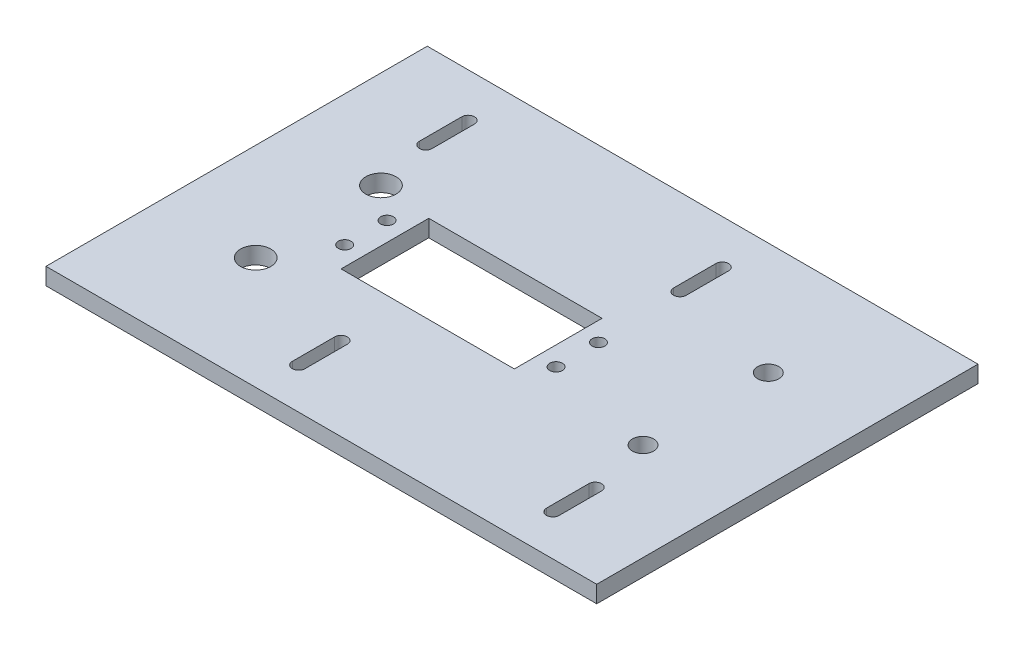
SolidWorks part; units mm, degrees
ref_plane "Front" through (0, 0, 0) normal (0, 0, 1) x (1, 0, 0)
ref_plane "Top" through (0, 0, 0) normal (0, 1, 0) x (1, 0, 0)
ref_plane "Right" through (0, 0, 0) normal (1, 0, 0) x (0, 0, -1)
sketch "Sketch1" plane through (0, 0, 0) normal (0, 1, 0) x (1, 0, 0)
  line L1 (-105, -51.6724) -> (25, -51.6724)
  line L2 (-105, -51.6724) -> (-105, 38.3276)
  line L3 (-105, 38.3276) -> (25, 38.3276)
  line L4 (25, -51.6724) -> (25, 38.3276)
  dimension "D2" = 90
  dimension "D1" = 130
extrude "Boss-Extrude1" add sketch "Sketch1" along normal blind 4
sketch "Sketch2" plane through (0, 4, 0) normal (0, 1, 0) x (1, 0, 0)
  line L1 (25, 38.3276) -> (-105, 38.3276) construction
  line L2 (-105, -51.6724) -> (25, -51.6724) construction
  line L3 (-40, 38.3276) -> (-40, -51.6724) construction
  point P0 (-40, -51.6724)
  point P1 (-40, 38.3276)
sketch "Sketch3" plane through (0, 4, 0) normal (0, 1, 0) x (1, 0, 0)
  line L0 (-92, 30.3276) -> (12, 30.3276) construction
  line L2 (25, 38.3276) -> (-105, 38.3276) construction
  line L3 (-105, -51.6724) -> (25, -51.6724) construction
  line L4 (-40, 38.3276) -> (-40, -51.6724) construction
  circle A0 centre (-92, 30.3276) radius 2.5
  circle A1 centre (12, 30.3276) radius 2.5
  circle A2 centre (12, -43.6724) radius 2.5
  circle A3 centre (-92, -43.6724) radius 2.5
  point P2 (-40, 30.3276)
  dimension "D2" = 5
  dimension "D4" = 5
  dimension "D5" = 5
  dimension "D1" = 5
  dimension "D3" = 104
  dimension "D6" = 8
  dimension "D7" = 8
extrude "Cut-Extrude1" [suppressed] cut sketch "Sketch3" against normal blind 10
sketch "Sketch4" plane through (0, 4, 0) normal (0, 1, 0) x (1, 0, 0)
  line L0 (-49, 14.3276) -> (-31, 14.3276) construction
  line L2 (25, 38.3276) -> (-105, 38.3276) construction
  line L3 (-40, 38.3276) -> (-40, -51.6724) construction
  circle A0 centre (-49, 14.3276) radius 1.15
  circle A1 centre (-31, 14.3276) radius 1.15
  point P4 (-40, 14.3276)
  dimension "D1" = 2.3
  dimension "D2" = 2.3
  dimension "D3" = 18
  dimension "D4" = 24
extrude "Cut-Extrude2" [suppressed] cut sketch "Sketch4" against normal blind 4
sketch "Sketch5" plane through (0, 0, 0) normal (0, -1, 0) x (-1, 0, 0)
  line L1 (-25, 38.3276) -> (105, 38.3276) construction
  line L2 (40, 38.3276) -> (40, -51.6724) construction
  circle A0 centre (40, 18.2946) radius 2
  dimension "D1" = 4
  dimension "D2" = 20.033
extrude "Cut-Extrude3" [suppressed] cut sketch "Sketch5" against normal blind 10
sketch "Sketch7" plane through (0, 4, 0) normal (0, 1, 0) x (1, 0, 0)
  line L0 (-82, 4.3933) -> (-82, -25.1724) construction
  line L1 (2, 11.8276) -> (2, -17.738) construction
  line L2 (25, 38.3276) -> (-105, 38.3276) construction
  line L3 (-40, 38.3276) -> (-40, -51.6724) construction
  line L4 (-105, -51.6724) -> (25, -51.6724) construction
  line L5 (-40, 38.3276) -> (-40, -51.6724) construction
  circle A4 centre (2, 11.8276) radius 3.65
  circle A5 centre (2, -17.738) radius 3.65
  circle A6 centre (-82, 4.3933) radius 3.57
  circle A7 centre (-82, -25.1724) radius 3.57
  point P16 (-40, -6.6724)
  dimension "D2" = 7.14
  dimension "D4" = 7.14
  dimension "D5" = 7.3
  dimension "D8" = 7.3
  dimension "D1" = 84
  dimension "D3" = 26.5
  dimension "D6" = 26.5
  dimension "D7" = 42
  dimension "D9" = 11.0657
  dimension "D10" = 11.0657
extrude "Cut-Extrude5" cut sketch "Sketch7" against normal blind 10
sketch "Sketch13" plane through (0, 4, 0) normal (0, 1, 0) x (1, 0, 0)
  line L0 (25, 38.3276) -> (-105, 38.3276) construction
  line L1 (-105, 38.3276) -> (-90, 38.3276)
  line L2 (-105, 38.3276) -> (-105, -51.6724)
  line L3 (-105, -51.6724) -> (-90, -51.6724)
  line L4 (-90, 38.3276) -> (-90, -51.6724)
  line L5 (10, 38.3276) -> (25, 38.3276)
  line L6 (10, 38.3276) -> (10, -51.6724)
  line L7 (10, -51.6724) -> (25, -51.6724)
  line L8 (25, 38.3276) -> (25, -51.6724)
  line L9 (25, -51.6724) -> (25, 38.3276) construction
  line L10 (-105, -51.6724) -> (25, -51.6724) construction
  dimension "D1" = 15
  dimension "D2" = 15
extrude "Cut-Extrude9" [suppressed] cut sketch "Sketch13" against normal blind 10
sketch "Sketch10" [suppressed] plane through (0, 4, 0) normal (0, 1, 0) x (1, 0, 0)
  line L0 (10, 38.3276) -> (-90, 38.3276) construction
  line L1 (-90, -51.6724) -> (10, -51.6724) construction
  line L2 (-45.5, 33.3276) -> (-34.5, 33.3276) construction
  line L3 (-45.5, -46.6724) -> (-34.5, -46.6724) construction
  line L4 (-24.3137, -2.9552) -> (-13, 8.3585) construction
  line L5 (-24.3137, -2.9552) -> (-13, -14.2689) construction
  line L6 (-40, 38.3276) -> (-40, -51.6724) construction
  line L7 (2, 11.8276) -> (2, -17.738) construction
  line L8 (-13, -14.2689) -> (-1.6863, -2.9552) construction
  line L9 (-1.6863, -2.9552) -> (-13, 8.3585) construction
  circle A0 centre (-45.5, 33.3276) radius 1.5
  circle A1 centre (-34.5, 33.3276) radius 1.5
  circle A2 centre (-45.5, -46.6724) radius 1.5
  circle A3 centre (-34.5, -46.6724) radius 1.5
  circle A4 centre (-13, -2.9552) radius 8
  circle A5 centre (-24.3137, -2.9552) radius 0.8
  circle A6 centre (-13, 8.3585) radius 0.8
  circle A7 centre (-1.6863, -2.9552) radius 0.8
  circle A8 centre (-13, -14.2689) radius 0.8
  circle A9 centre (-24.3137, -14.2689) radius 5
  point P12 (-40, 33.3276)
  point P27 (2, -2.9552)
  point P36 (-13, -2.9552)
  dimension "D1" = 3
  dimension "D5" = 3
  dimension "D6" = 3
  dimension "D7" = 3
  dimension "D8" = 16
  dimension "D11" = 1.6
  dimension "D12" = 1.6
  dimension "D13" = 1.6
  dimension "D14" = 1.6
  dimension "D16" = 10
  dimension "D2" = 11
  dimension "D3" = 5
  dimension "D4" = 5
  dimension "D9" = 16
  dimension "D10" = 16
  dimension "D18" = 11.3137
  dimension "D19" = 11.3137
  dimension "D15" = 15
extrude "Cut-Extrude7" [suppressed] cut sketch "Sketch10" against normal blind 10
sketch "Sketch6" plane through (0, 0, 0) normal (0, -1, 0) x (1, 0, 0)
  line L0 (-69.6394, 7.0305) -> (-28.7394, 7.0305) construction
  line L1 (-69.6394, 17.3805) -> (-28.7394, 17.3805)
  line L2 (-69.6394, 17.3805) -> (-69.6394, -3.3195)
  line L3 (-69.6394, -3.3195) -> (-28.7394, -3.3195)
  line L4 (-28.7394, 17.3805) -> (-28.7394, -3.3195)
  line L6 (-74.1394, 2.0305) -> (-74.1394, 12.0305) construction
  circle A0 centre (-74.1394, 12.0305) radius 1.5
  circle A1 centre (-24.2394, 12.0305) radius 1.5
  circle A2 centre (-74.1394, 2.0305) radius 1.5
  circle A3 centre (-24.2394, 2.0305) radius 1.5
  point P13 (-49.1894, 7.0305)
  point P19 (-74.1394, 7.0305)
  dimension "D3" = 3
  dimension "D4" = 3
  dimension "D9" = 3
  dimension "D10" = 3
  dimension "D1" = 40.9
  dimension "D2" = 20.7
  dimension "D5" = 4.5
  dimension "D6" = 4.5
  dimension "D11" = 10
extrude "Cut-Extrude4" cut sketch "Sketch6" against normal blind 4
sketch "Sketch11" plane through (0, 4, 0) normal (0, 1, 0) x (1, 0, 0)
  line L0 (-74.1394, -12.0305) -> (8.7, -12.0305) construction
sketch "Sketch12" plane through (0, 4, 0) normal (0, 1, 0) x (1, 0, 0)
  line L0 (-85, 27.9695) -> (-85, 17.9695) construction
  line L1 (-85, 27.9695) -> (-25, 27.9695) construction
  line L2 (-55, -32.0305) -> (-55, -42.0305) construction
  line L3 (-105, 38.3276) -> (-105, -51.6724) construction
  line L4 (-49.1894, 3.3195) -> (-49.1894, -17.3805) construction
  line L5 (25, -51.6724) -> (25, 38.3276) construction
  line L6 (-69.6394, 3.3195) -> (-28.7394, 3.3195) construction
  line L7 (-28.7394, -17.3805) -> (-69.6394, -17.3805) construction
  line L8 (-55, -42.0305) -> (5, -42.0305) construction
  line L9 (-86.5, 27.9695) -> (-86.5, 17.9695)
  line L10 (-83.5, 17.9695) -> (-83.5, 27.9695)
  line L11 (-23.5, 27.9695) -> (-23.5, 17.9695)
  line L13 (-26.5, 17.9695) -> (-26.5, 27.9695)
  line L14 (-53.5, -32.0305) -> (-53.5, -42.0305)
  line L15 (-56.5, -32.0305) -> (-56.5, -42.0305)
  line L16 (3.5, -42.0305) -> (3.5, -32.0305)
  line L17 (6.5, -32.0305) -> (6.5, -42.0305)
  circle A0 centre (-85, 27.9695) radius 1.5
  circle A1 centre (-25, 27.9695) radius 1.5
  circle A2 centre (-55, -42.0305) radius 1.5
  circle A3 centre (5, -42.0305) radius 1.5
  circle A4 centre (-85, 17.9695) radius 1.5
  circle A5 centre (-25, 17.9695) radius 1.5
  circle A6 centre (5, -32.0305) radius 1.5
  circle A7 centre (-55, -32.0305) radius 1.5
  point P20 (-49.1894, -7.0305)
  point P27 (-55, -37.0305)
  point P28 (-85, 22.9695)
  dimension "D3" = 3
  dimension "D4" = 3
  dimension "D1" = 3
  dimension "D16" = 10
  dimension "D2" = 3
  dimension "D11" = 3
  dimension "D12" = 3
  dimension "D13" = 3
  dimension "D14" = 3
  dimension "D6" = 60
  dimension "D8" = 60
  dimension "D7" = 20
  dimension "D9" = 20
  dimension "D15" = 10
  dimension "D5" = 30
  dimension "D10" = 30
extrude "Cut-Extrude8" cut sketch "Sketch12" against normal blind 10 contours A7 L15 A2 L14 | A2 | A7 | A6 | A3 | A1 | A5 | A0 | A4 | A6 L16 A3 L17 | A5 L11 A1 L13 | A4 L10 A0 L9 region at (-85, 4, -22.9695) region at (-85, 4, -27.9695) region at (-85, 4, -17.9695) region at (-25, 4, -27.9695) region at (-25, 4, -22.9695) region at (-25, 4, -17.9695) region at (-55, 4, 32.0305) region at (-55, 4, 37.0305) region at (-55, 4, 42.0305) region at (5, 4, 37.0305) region at (5, 4, 42.0305) region at (5, 4, 32.0305)
sketch "Sketch14" plane through (0, 4, 0) normal (0, 1, 0) x (1, 0, 0)
  line L0 (2, 11.8276) -> (2, -17.738) construction
  line L1 (-5.8425, 19.5277) -> (9.8425, 19.5277)
  line L2 (-5.8425, 19.5277) -> (-5.8425, -25.4381)
  line L3 (-5.8425, -25.4381) -> (9.8425, -25.4381)
  line L4 (9.8425, 19.5277) -> (9.8425, -25.4381)
  line L6 (23.551, -3.9962) -> (23.6558, -3.94) construction
  circle A0 centre (2, 11.8276) radius 2.5
  circle A1 centre (2, -17.738) radius 2.5
  point P10 (2, -2.9552)
  point P14 (-5.8425, -2.9552)
  point P15 (2, 19.5277)
  dimension "D3" = 5
  dimension "D4" = 5
  dimension "D1" = 15.685
  dimension "D2" = 44.9658
extrude "Boss-Extrude2" add sketch "Sketch14" against normal through all
equation "\"gripper_mainPlate_WheelDist\"=104"
equation "\"D5@Sketch3\"=\"D4@Sketch3\""
equation "\"D1@Sketch3\"=\"D4@Sketch3\""
equation "\"D2@Sketch3\"=\"D4@Sketch3\""
equation "\"D7@Sketch3\"=\"D6@Sketch3\""
equation "\"D2@Sketch4\"=\"D1@Sketch4\""
equation "\"D4@Sketch6\"=\"D3@Sketch6\""
equation "\"D5@Sketch6\"=\"D6@Sketch6\""
equation "\"D4@Sketch10\"=\"D3@Sketch10\""
equation "\"D5@Sketch10\"=\"D1@Sketch10\""
equation "\"D6@Sketch10\"=\"D1@Sketch10\""
equation "\"D7@Sketch10\"=\"D1@Sketch10\""
equation "\"D4@Sketch7\"=\"D2@Sketch7\""
equation "\"D14@Sketch10\"=\"D11@Sketch10\""
equation "\"D13@Sketch10\"=\"D11@Sketch10\""
equation "\"D12@Sketch10\"=\"D11@Sketch10\""
equation "\"D2@Sketch12\"=\"D1@Sketch12\""
equation "\"D3@Sketch12\"=\"D1@Sketch12\""
equation "\"D4@Sketch12\"=\"D1@Sketch12\""
equation "\"D9@Sketch6\"=\"D3@Sketch6\""
equation "\"D10@Sketch6\"=\"D3@Sketch6\""
equation "\"D8@Sketch12\"=\"D6@Sketch12\""
equation "\"D2@Sketch13\"=\"D1@Sketch13\""
equation "\"D7@Sketch12\"=\"D9@Sketch12\""
equation "\"D19@Sketch10\"=\"D18@Sketch10\""
equation "\"D16@Sketch12\"=\"D15@Sketch12\""
equation "\"D11@Sketch12\"=\"D3@Sketch12\""
equation "\"D12@Sketch12\"=\"D4@Sketch12\""
equation "\"D13@Sketch12\"=\"D2@Sketch12\""
equation "\"D14@Sketch12\"=\"D1@Sketch12\""
equation "\"D10@Sketch12\"=\"D5@Sketch12\""
equation "\"D6@Sketch7\"=\"D3@Sketch7\""
equation "\"D7@Sketch7\"=\"D1@Sketch7\"/2"
equation "\"D10@Sketch7\"=\"D9@Sketch7\""
equation "\"D8@Sketch7\"=\"D5@Sketch7\""
equation "\"D4@Sketch14\"=\"D3@Sketch14\""
